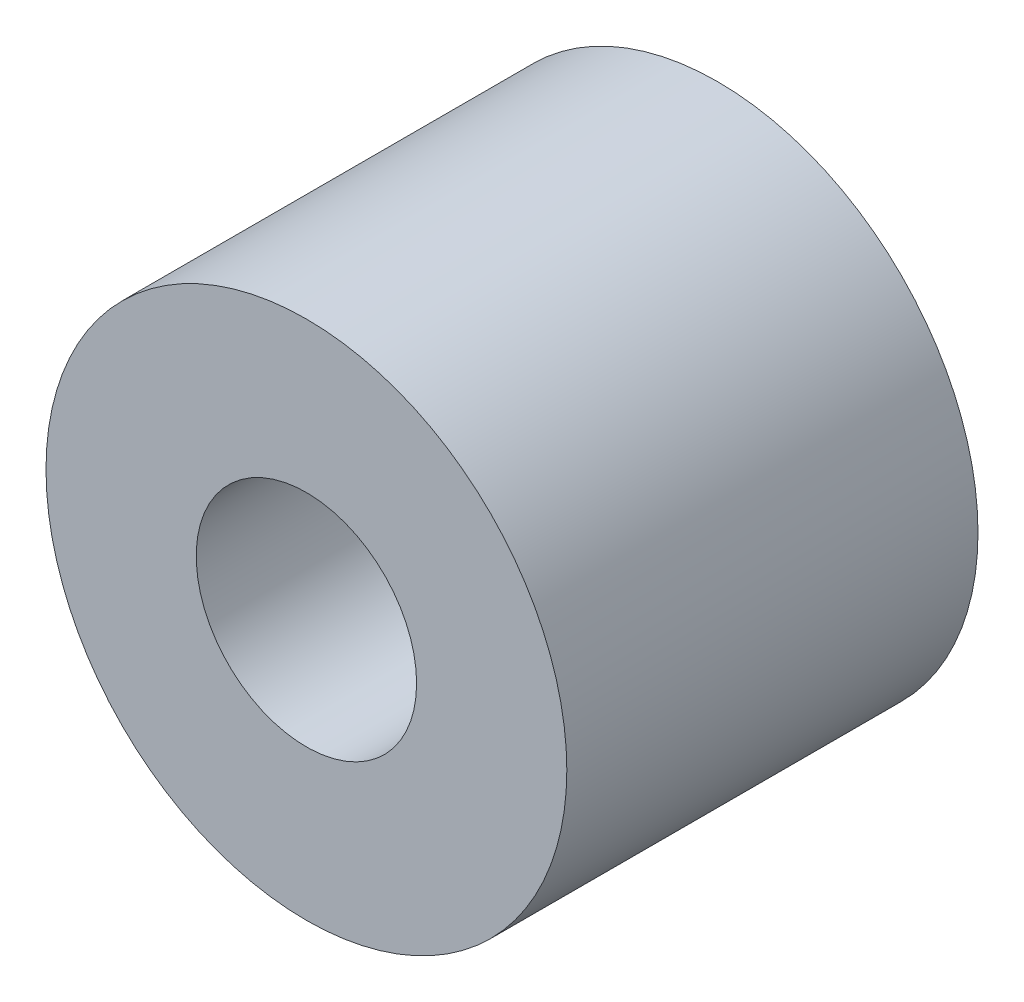
SolidWorks part; units mm, degrees
ref_plane "Front Plane" through (0, 0, 0) normal (0, 0, 1) x (1, 0, 0)
ref_plane "Top Plane" through (0, 0, 0) normal (0, 1, 0) x (1, 0, 0)
ref_plane "Right Plane" through (0, 0, 0) normal (1, 0, 0) x (0, 0, -1)
sketch "Sketch1" plane through (0, 0, 0) normal (0, 0, 1) x (1, 0, 0)
  circle A0 centre (0, 0) radius 6.0325
  dimension "D1" = 12.065
extrude "Boss-Extrude1" add sketch "Sketch1" along normal mid plane 9.525
sketch "Sketch2" plane through (0, 0, 4.7625) normal (0, 0, 1) x (1, 0, 0)
  point P0 (0, 0)
hole_wizard "Tap Drill for 1/4-20 Tap1" positions "Sketch2" profile "Sketch3" hole size "1/4-20" standard "ANSI Inch" end condition through all
sketch "Sketch3" plane through (0, 0, 4.7625) normal (1, 0, 0) x (0, -1, 0)
  line L0 (0, 0) -> (0, 9.525)
  line L1 (0, 9.525) -> (2.5527, 9.525)
  line L2 (2.5527, 9.525) -> (2.5527, 0)
  line L5 (2.5527, 0) -> (0, 0)
  line L11 (0, -6.35) -> (0, 107.95) construction
  dimension "Thru Hole Dia." = 5.1054
  dimension "Thru Hole Depth" = 9.525
cosmetic thread "Cosmetic Thread1"
equation "\"AIRFRAME_OD\"= 3.091in"
equation "\"AIRFRAME_ID\"= 3.00in"
equation "\"FLAT_T\"= 0.125in"
equation "\"NOSE_EXP_L\"= 3.5in"
equation "\"NOSE_SHOULDER_L\"= 5in"
equation "\"MAIN_L\"= 30in"
equation "\"RECO_COUP_L\"= 6in"
equation "\"RECO_SWITCH_L\"= 1.5in"
equation "\"DROGUE_L\"= 14in"
equation "\"ATS_FORE_COUP_L\"= 4in"
equation "\"ATS_AFT_COUP_L\"= 2.5in"
equation "\"LOWER_L\"= 16in"
equation "\"FIN_N\"= 4"
equation "\"CR_AFT_X\"= 0.5in"
equation "\"CR_FORE_X\"= 6in"
